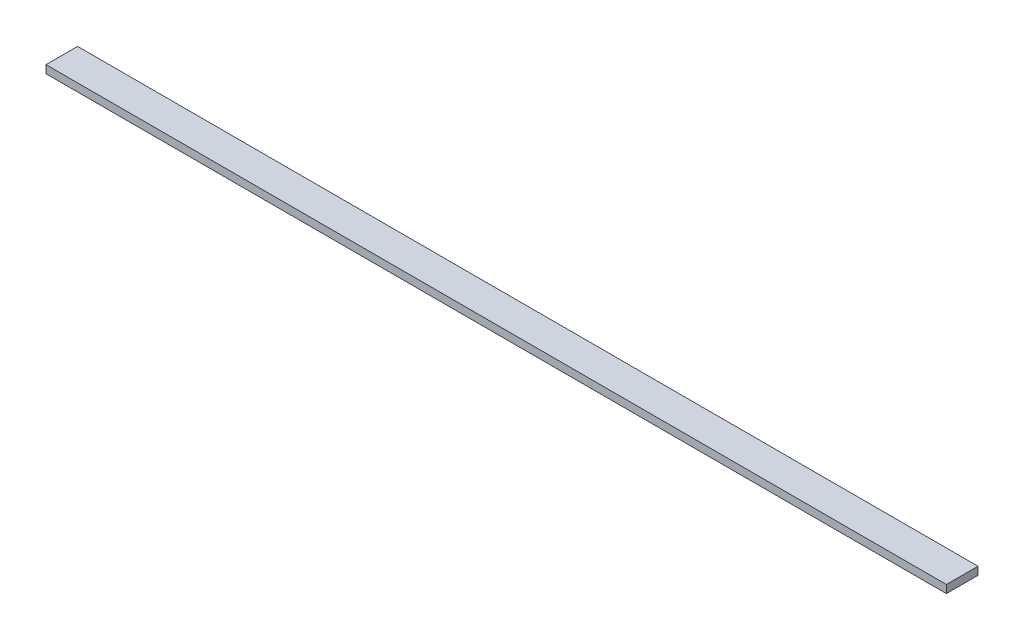
SolidWorks part; units mm, degrees
ref_plane "Front Plane" through (0, 0, 0) normal (0, 0, 1) x (1, 0, 0)
ref_plane "Top Plane" through (0, 0, 0) normal (0, 1, 0) x (1, 0, 0)
ref_plane "Right Plane" through (0, 0, 0) normal (1, 0, 0) x (0, 0, -1)
sketch "Sketch1" plane through (0, 0, 0) normal (0, 1, 0) x (1, 0, 0)
  line L1 (-361.95, -12.7) -> (361.95, -12.7)
  line L2 (-361.95, -12.7) -> (-361.95, 12.7)
  line L3 (-361.95, 12.7) -> (361.95, 12.7)
  line L4 (361.95, -12.7) -> (361.95, 12.7)
  line L5 (-361.95, -12.7) -> (361.95, 12.7) construction
  line L6 (-361.95, 12.7) -> (361.95, -12.7) construction
  point P0 (0, 0)
  dimension "D1" = 723.9
  dimension "D2" = 25.4
extrude "Boss-Extrude1" add sketch "Sketch1" along normal blind 6.35
equation "\"horizontal-component-length\"= \"railing-width\" - \"railing padding\""
equation "\"horizontal-component-width\"= 1in"
equation "\"D1@Sketch1\"=\"horizontal-component-length\""
equation "\"D2@Sketch1\"=\"horizontal-component-width\""
equation "\"material-thickness\"= .25in"
equation "\"D1@Boss-Extrude1\"=\"material-thickness\""
equation "\"railing-width\" = 29in"
equation "\"railing padding\"= .5in"
